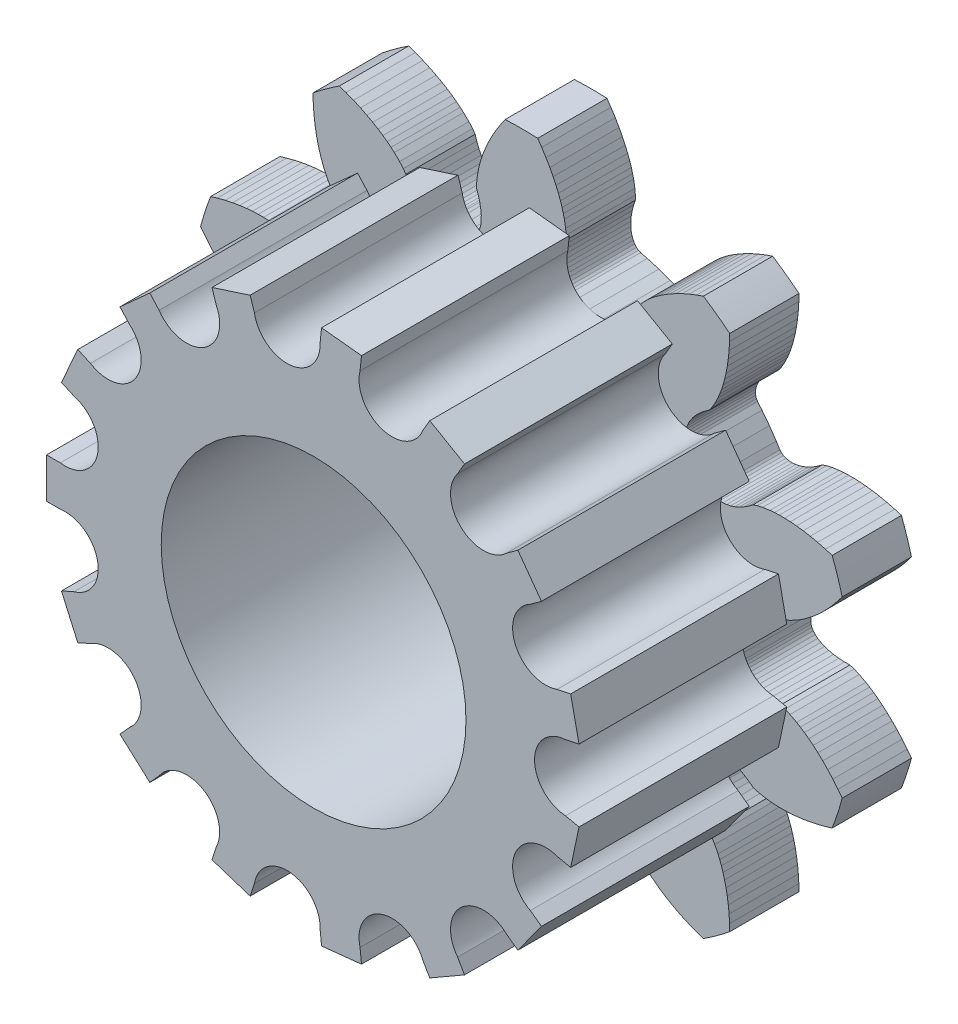
SolidWorks part; units mm, degrees
ref_plane "Front Plane" through (0, 0, 0) normal (0, 0, 1) x (1, 0, 0)
ref_plane "Top Plane" through (0, 0, 0) normal (0, 1, 0) x (1, 0, 0)
ref_plane "Right Plane" through (0, 0, 0) normal (1, 0, 0) x (0, 0, -1)
sketch "Model" plane through (0, 0, 0) normal (0, 0, 1) x (1, 0, 0)
  line L0 (44.9714, -18.1936) -> (45.0072, -17.6135)
  line L1 (45.0072, -17.6135) -> (45.064, -17.0676)
  line L2 (45.064, -17.0676) -> (45.1386, -16.5586)
  line L3 (45.1386, -16.5586) -> (45.2286, -16.0837)
  line L4 (45.2286, -16.0837) -> (45.3307, -15.6464)
  line L5 (45.3307, -15.6464) -> (45.4422, -15.245)
  line L6 (45.4422, -15.245) -> (45.5601, -14.8808)
  line L7 (45.5601, -14.8808) -> (45.6817, -14.5526)
  line L8 (45.6817, -14.5526) -> (45.8046, -14.2592)
  line L9 (45.8046, -14.2592) -> (46.0415, -13.7787)
  line L10 (46.0415, -13.7787) -> (46.2493, -13.433)
  line L11 (46.2493, -13.433) -> (46.4387, -13.1745)
  line L12 (46.4387, -13.1745) -> (46.7566, -12.9496)
  line L13 (46.7566, -12.9496) -> (47.0768, -12.6883)
  line L14 (47.0768, -12.6883) -> (47.3522, -12.4243)
  line L15 (47.3522, -12.4243) -> (47.5834, -12.1609)
  line L16 (47.5834, -12.1609) -> (47.7708, -11.9014)
  line L17 (47.7708, -11.9014) -> (47.9153, -11.6488)
  line L18 (47.9153, -11.6488) -> (48.0178, -11.4063)
  line L19 (48.0178, -11.4063) -> (48.0795, -11.177)
  line L20 (48.0795, -11.177) -> (48.1017, -10.9637)
  line L21 (48.1017, -10.9637) -> (48.086, -10.7695)
  line L22 (48.086, -10.7695) -> (48.034, -10.597)
  line L23 (48.034, -10.597) -> (47.9475, -10.4489)
  line L24 (47.9475, -10.4489) -> (47.6302, -10.0694)
  line L25 (47.6302, -10.0694) -> (47.0962, -9.3752)
  line L26 (47.0962, -9.3752) -> (46.601, -8.6528)
  line L27 (46.601, -8.6528) -> (46.3381, -8.2337)
  line L28 (46.3381, -8.2337) -> (46.224, -8.1057)
  line L29 (46.224, -8.1057) -> (46.076, -8.0029)
  line L30 (46.076, -8.0029) -> (45.8961, -7.9279)
  line L31 (45.8961, -7.9279) -> (45.6864, -7.8832)
  line L32 (45.6864, -7.8832) -> (45.4493, -7.871)
  line L33 (45.4493, -7.871) -> (45.187, -7.8936)
  line L34 (45.187, -7.8936) -> (44.9021, -7.9529)
  line L35 (44.9021, -7.9529) -> (44.5973, -8.051)
  line L36 (44.5973, -8.051) -> (44.2754, -8.1894)
  line L37 (44.2754, -8.1894) -> (43.9392, -8.3698)
  line L38 (43.9392, -8.3698) -> (43.5918, -8.5936)
  line L39 (43.5918, -8.5936) -> (43.2796, -8.8264)
  line L40 (43.2796, -8.8264) -> (42.9752, -8.9266)
  line L41 (42.9752, -8.9266) -> (42.5822, -9.0175)
  line L42 (42.5822, -9.0175) -> (42.052, -9.0943)
  line L43 (42.052, -9.0943) -> (41.735, -9.1205)
  line L44 (41.735, -9.1205) -> (41.3854, -9.1348)
  line L45 (41.3854, -9.1348) -> (41.0026, -9.1343)
  line L46 (41.0026, -9.1343) -> (40.5863, -9.1164)
  line L47 (40.5863, -9.1164) -> (40.1389, -9.0783)
  line L48 (40.1389, -9.0783) -> (39.6594, -9.0172)
  line L49 (39.6594, -9.0172) -> (39.1523, -8.9308)
  line L50 (39.1523, -8.9308) -> (38.6155, -8.8161)
  line L51 (38.6155, -8.8161) -> (38.0528, -8.671)
  line L52 (38.0528, -8.671) -> (37.565, -8.5243)
  line L53 (36.8392, -6.2906) -> (37.1476, -5.8853)
  line L54 (37.1476, -5.8853) -> (37.5176, -5.4371)
  line L55 (37.5176, -5.4371) -> (37.8845, -5.0288)
  line L56 (37.8845, -5.0288) -> (38.244, -4.6608)
  line L57 (38.244, -4.6608) -> (38.596, -4.3295)
  line L58 (38.596, -4.3295) -> (38.9355, -4.0358)
  line L59 (38.9355, -4.0358) -> (39.2618, -3.7766)
  line L60 (39.2618, -3.7766) -> (39.5712, -3.5512)
  line L61 (39.5712, -3.5512) -> (39.8624, -3.3572)
  line L62 (39.8624, -3.3572) -> (40.1343, -3.1921)
  line L63 (40.1343, -3.1921) -> (40.6084, -2.9426)
  line L64 (40.6084, -2.9426) -> (40.9797, -2.7851)
  line L65 (40.9797, -2.7851) -> (41.2849, -2.6873)
  line L66 (41.2849, -2.6873) -> (41.6743, -2.6921)
  line L67 (41.6743, -2.6921) -> (42.0869, -2.669)
  line L68 (42.0869, -2.669) -> (42.4649, -2.6173)
  line L69 (42.4649, -2.6173) -> (42.8067, -2.5401)
  line L70 (42.8067, -2.5401) -> (43.1109, -2.4403)
  line L71 (43.1109, -2.4403) -> (43.3763, -2.3209)
  line L72 (43.3763, -2.3209) -> (43.6018, -2.1849)
  line L73 (43.6018, -2.1849) -> (43.7865, -2.0357)
  line L74 (43.7865, -2.0357) -> (43.9298, -1.8762)
  line L75 (43.9298, -1.8762) -> (44.0312, -1.7098)
  line L76 (44.0312, -1.7098) -> (44.0905, -1.5397)
  line L77 (44.0905, -1.5397) -> (44.1076, -1.369)
  line L78 (44.1076, -1.369) -> (44.074, -0.8755)
  line L79 (44.074, -0.8755) -> (44.05, 0)
  line L80 (44.05, 0) -> (44.074, 0.8755)
  line L81 (44.074, 0.8755) -> (44.1076, 1.369)
  line L82 (44.1076, 1.369) -> (44.0905, 1.5397)
  line L83 (44.0905, 1.5397) -> (44.0312, 1.7098)
  line L84 (44.0312, 1.7098) -> (43.9298, 1.8762)
  line L85 (43.9298, 1.8762) -> (43.7865, 2.0357)
  line L86 (43.7865, 2.0357) -> (43.6018, 2.1849)
  line L87 (43.6018, 2.1849) -> (43.3763, 2.3209)
  line L88 (43.3763, 2.3209) -> (43.1109, 2.4403)
  line L89 (43.1109, 2.4403) -> (42.8067, 2.5401)
  line L90 (42.8067, 2.5401) -> (42.4649, 2.6173)
  line L91 (42.4649, 2.6173) -> (42.0869, 2.669)
  line L92 (42.0869, 2.669) -> (41.6743, 2.6921)
  line L93 (41.6743, 2.6921) -> (41.2849, 2.6873)
  line L94 (41.2849, 2.6873) -> (40.9797, 2.7851)
  line L95 (40.9797, 2.7851) -> (40.6084, 2.9426)
  line L96 (40.6084, 2.9426) -> (40.1343, 3.1921)
  line L97 (40.1343, 3.1921) -> (39.8624, 3.3572)
  line L98 (39.8624, 3.3572) -> (39.5712, 3.5512)
  line L99 (39.5712, 3.5512) -> (39.2618, 3.7766)
  line L100 (39.2618, 3.7766) -> (38.9355, 4.0358)
  line L101 (38.9355, 4.0358) -> (38.596, 4.3295)
  line L102 (38.596, 4.3295) -> (38.244, 4.6608)
  line L103 (38.244, 4.6608) -> (37.8845, 5.0288)
  line L104 (37.8845, 5.0288) -> (37.5176, 5.4371)
  line L105 (37.5176, 5.4371) -> (37.1476, 5.8853)
  line L106 (37.1476, 5.8853) -> (36.8392, 6.2906)
  line L107 (37.565, 8.5243) -> (38.0528, 8.671)
  line L108 (38.0528, 8.671) -> (38.6155, 8.8161)
  line L109 (38.6155, 8.8161) -> (39.1523, 8.9308)
  line L110 (39.1523, 8.9308) -> (39.6594, 9.0172)
  line L111 (39.6594, 9.0172) -> (40.1389, 9.0783)
  line L112 (40.1389, 9.0783) -> (40.5863, 9.1164)
  line L113 (40.5863, 9.1164) -> (41.0026, 9.1343)
  line L114 (41.0026, 9.1343) -> (41.3854, 9.1348)
  line L115 (41.3854, 9.1348) -> (41.735, 9.1205)
  line L116 (41.735, 9.1205) -> (42.052, 9.0943)
  line L117 (42.052, 9.0943) -> (42.5822, 9.0175)
  line L118 (42.5822, 9.0175) -> (42.9752, 8.9266)
  line L119 (42.9752, 8.9266) -> (43.2796, 8.8264)
  line L120 (43.2796, 8.8264) -> (43.5918, 8.5936)
  line L121 (43.5918, 8.5936) -> (43.9392, 8.3698)
  line L122 (43.9392, 8.3698) -> (44.2754, 8.1894)
  line L123 (44.2754, 8.1894) -> (44.5973, 8.051)
  line L124 (44.5973, 8.051) -> (44.9021, 7.9529)
  line L125 (44.9021, 7.9529) -> (45.187, 7.8936)
  line L126 (45.187, 7.8936) -> (45.4493, 7.871)
  line L127 (45.4493, 7.871) -> (45.6864, 7.8832)
  line L128 (45.6864, 7.8832) -> (45.8961, 7.9279)
  line L129 (45.8961, 7.9279) -> (46.076, 8.0029)
  line L130 (46.076, 8.0029) -> (46.224, 8.1057)
  line L131 (46.224, 8.1057) -> (46.3381, 8.2337)
  line L132 (46.3381, 8.2337) -> (46.601, 8.6528)
  line L133 (46.601, 8.6528) -> (47.0962, 9.3752)
  line L134 (47.0962, 9.3752) -> (47.6302, 10.0694)
  line L135 (47.6302, 10.0694) -> (47.9475, 10.4489)
  line L136 (47.9475, 10.4489) -> (48.034, 10.597)
  line L137 (48.034, 10.597) -> (48.086, 10.7695)
  line L138 (48.086, 10.7695) -> (48.1017, 10.9637)
  line L139 (48.1017, 10.9637) -> (48.0795, 11.177)
  line L140 (48.0795, 11.177) -> (48.0178, 11.4063)
  line L141 (48.0178, 11.4063) -> (47.9153, 11.6488)
  line L142 (47.9153, 11.6488) -> (47.7708, 11.9014)
  line L143 (47.7708, 11.9014) -> (47.5834, 12.1609)
  line L144 (47.5834, 12.1609) -> (47.3522, 12.4243)
  line L145 (47.3522, 12.4243) -> (47.0768, 12.6883)
  line L146 (47.0768, 12.6883) -> (46.7566, 12.9496)
  line L147 (46.7566, 12.9496) -> (46.4387, 13.1745)
  line L148 (46.4387, 13.1745) -> (46.2493, 13.433)
  line L149 (46.2493, 13.433) -> (46.0415, 13.7787)
  line L150 (46.0415, 13.7787) -> (45.8046, 14.2592)
  line L151 (45.8046, 14.2592) -> (45.6817, 14.5526)
  line L152 (45.6817, 14.5526) -> (45.5601, 14.8808)
  line L153 (45.5601, 14.8808) -> (45.4422, 15.245)
  line L154 (45.4422, 15.245) -> (45.3307, 15.6464)
  line L155 (45.3307, 15.6464) -> (45.2286, 16.0837)
  line L156 (45.2286, 16.0837) -> (45.1386, 16.5586)
  line L157 (45.1386, 16.5586) -> (45.064, 17.0676)
  line L158 (45.064, 17.0676) -> (45.0072, 17.6135)
  line L159 (45.0072, 17.6135) -> (44.9714, 18.1936)
  line L160 (44.9714, 18.1936) -> (44.9601, 18.7028)
  line L161 (46.8602, 20.0833) -> (47.341, 19.9152)
  line L162 (47.341, 19.9152) -> (47.8816, 19.7019)
  line L163 (47.8816, 19.7019) -> (48.3833, 19.4792)
  line L164 (48.3833, 19.4792) -> (48.8443, 19.2509)
  line L165 (48.8443, 19.2509) -> (49.2681, 19.0186)
  line L166 (49.2681, 19.0186) -> (49.6525, 18.7864)
  line L167 (49.6525, 18.7864) -> (49.9998, 18.5562)
  line L168 (49.9998, 18.5562) -> (50.3097, 18.3316)
  line L169 (50.3097, 18.3316) -> (50.5842, 18.1146)
  line L170 (50.5842, 18.1146) -> (50.8253, 17.907)
  line L171 (50.8253, 17.907) -> (51.2091, 17.5332)
  line L172 (51.2091, 17.5332) -> (51.4736, 17.2287)
  line L173 (51.4736, 17.2287) -> (51.6609, 16.9687)
  line L174 (51.6609, 16.9687) -> (51.7767, 16.5968)
  line L175 (51.7767, 16.5968) -> (51.9262, 16.2116)
  line L176 (51.9262, 16.2116) -> (52.0921, 15.8681)
  line L177 (52.0921, 15.8681) -> (52.2712, 15.5668)
  line L178 (52.2712, 15.5668) -> (52.4601, 15.3084)
  line L179 (52.4601, 15.3084) -> (52.6557, 15.0929)
  line L180 (52.6557, 15.0929) -> (52.8547, 14.9205)
  line L181 (52.8547, 14.9205) -> (53.0537, 14.7909)
  line L182 (53.0537, 14.7909) -> (53.2496, 14.7039)
  line L183 (53.2496, 14.7039) -> (53.4392, 14.6588)
  line L184 (53.4392, 14.6588) -> (53.6194, 14.655)
  line L185 (53.6194, 14.655) -> (53.7869, 14.6915)
  line L186 (53.7869, 14.6915) -> (54.2459, 14.876)
  line L187 (54.2459, 14.876) -> (55.0712, 15.1694)
  line L188 (55.0712, 15.1694) -> (55.9113, 15.4171)
  line L189 (55.9113, 15.4171) -> (56.391, 15.5376)
  line L190 (56.391, 15.5376) -> (56.548, 15.6066)
  line L191 (56.548, 15.6066) -> (56.6915, 15.7156)
  line L192 (56.6915, 15.7156) -> (56.8184, 15.8635)
  line L193 (56.8184, 15.8635) -> (56.9258, 16.049)
  line L194 (56.9258, 16.049) -> (57.0107, 16.2708)
  line L195 (57.0107, 16.2708) -> (57.0703, 16.5273)
  line L196 (57.0703, 16.5273) -> (57.1018, 16.8165)
  line L197 (57.1018, 16.8165) -> (57.1028, 17.1367)
  line L198 (57.1028, 17.1367) -> (57.0706, 17.4857)
  line L199 (57.0706, 17.4857) -> (57.0029, 17.8611)
  line L200 (57.0029, 17.8611) -> (56.8974, 18.2607)
  line L201 (56.8974, 18.2607) -> (56.7725, 18.6296)
  line L202 (56.7725, 18.6296) -> (56.7712, 18.95)
  line L203 (56.7712, 18.95) -> (56.8063, 19.3518)
  line L204 (56.8063, 19.3518) -> (56.897, 19.8798)
  line L205 (56.897, 19.8798) -> (56.97, 20.1894)
  line L206 (56.97, 20.1894) -> (57.0646, 20.5264)
  line L207 (57.0646, 20.5264) -> (57.1833, 20.8903)
  line L208 (57.1833, 20.8903) -> (57.329, 21.2806)
  line L209 (57.329, 21.2806) -> (57.5034, 21.6944)
  line L210 (57.5034, 21.6944) -> (57.7097, 22.1315)
  line L211 (57.7097, 22.1315) -> (57.9486, 22.5871)
  line L212 (57.9486, 22.5871) -> (58.2236, 23.0622)
  line L213 (58.2236, 23.0622) -> (58.5355, 23.5525)
  line L214 (58.5355, 23.5525) -> (58.8257, 23.9711)
  line L215 (61.1743, 23.9711) -> (61.4645, 23.5525)
  line L216 (61.4645, 23.5525) -> (61.7764, 23.0622)
  line L217 (61.7764, 23.0622) -> (62.0514, 22.5871)
  line L218 (62.0514, 22.5871) -> (62.2903, 22.1315)
  line L219 (62.2903, 22.1315) -> (62.4966, 21.6944)
  line L220 (62.4966, 21.6944) -> (62.671, 21.2806)
  line L221 (62.671, 21.2806) -> (62.8167, 20.8903)
  line L222 (62.8167, 20.8903) -> (62.9354, 20.5264)
  line L223 (62.9354, 20.5264) -> (63.03, 20.1894)
  line L224 (63.03, 20.1894) -> (63.103, 19.8798)
  line L225 (63.103, 19.8798) -> (63.1937, 19.3518)
  line L226 (63.1937, 19.3518) -> (63.2288, 18.95)
  line L227 (63.2288, 18.95) -> (63.2275, 18.6296)
  line L228 (63.2275, 18.6296) -> (63.1026, 18.2607)
  line L229 (63.1026, 18.2607) -> (62.9971, 17.8611)
  line L230 (62.9971, 17.8611) -> (62.9294, 17.4857)
  line L231 (62.9294, 17.4857) -> (62.8972, 17.1367)
  line L232 (62.8972, 17.1367) -> (62.8982, 16.8165)
  line L233 (62.8982, 16.8165) -> (62.9297, 16.5273)
  line L234 (62.9297, 16.5273) -> (62.9893, 16.2708)
  line L235 (62.9893, 16.2708) -> (63.0742, 16.049)
  line L236 (63.0742, 16.049) -> (63.1816, 15.8635)
  line L237 (63.1816, 15.8635) -> (63.3085, 15.7156)
  line L238 (63.3085, 15.7156) -> (63.452, 15.6066)
  line L239 (63.452, 15.6066) -> (63.609, 15.5376)
  line L240 (63.609, 15.5376) -> (64.0887, 15.4171)
  line L241 (64.0887, 15.4171) -> (64.9288, 15.1694)
  line L242 (64.9288, 15.1694) -> (65.7541, 14.876)
  line L243 (65.7541, 14.876) -> (66.2131, 14.6915)
  line L244 (66.2131, 14.6915) -> (66.3806, 14.655)
  line L245 (66.3806, 14.655) -> (66.5608, 14.6588)
  line L246 (66.5608, 14.6588) -> (66.7504, 14.7039)
  line L247 (66.7504, 14.7039) -> (66.9463, 14.7909)
  line L248 (66.9463, 14.7909) -> (67.1453, 14.9205)
  line L249 (67.1453, 14.9205) -> (67.3443, 15.0929)
  line L250 (67.3443, 15.0929) -> (67.5399, 15.3084)
  line L251 (67.5399, 15.3084) -> (67.7288, 15.5668)
  line L252 (67.7288, 15.5668) -> (67.9079, 15.8681)
  line L253 (67.9079, 15.8681) -> (68.0738, 16.2116)
  line L254 (68.0738, 16.2116) -> (68.2233, 16.5968)
  line L255 (68.2233, 16.5968) -> (68.3391, 16.9687)
  line L256 (68.3391, 16.9687) -> (68.5264, 17.2287)
  line L257 (68.5264, 17.2287) -> (68.7909, 17.5332)
  line L258 (68.7909, 17.5332) -> (69.1747, 17.907)
  line L259 (69.1747, 17.907) -> (69.4158, 18.1146)
  line L260 (69.4158, 18.1146) -> (69.6903, 18.3316)
  line L261 (69.6903, 18.3316) -> (70.0002, 18.5562)
  line L262 (70.0002, 18.5562) -> (70.3475, 18.7864)
  line L263 (70.3475, 18.7864) -> (70.7319, 19.0186)
  line L264 (70.7319, 19.0186) -> (71.1557, 19.2509)
  line L265 (71.1557, 19.2509) -> (71.6167, 19.4792)
  line L266 (71.6167, 19.4792) -> (72.1184, 19.7019)
  line L267 (72.1184, 19.7019) -> (72.659, 19.9152)
  line L268 (72.659, 19.9152) -> (73.1398, 20.0833)
  line L269 (75.0399, 18.7028) -> (75.0286, 18.1936)
  line L270 (75.0286, 18.1936) -> (74.9928, 17.6135)
  line L271 (74.9928, 17.6135) -> (74.936, 17.0676)
  line L272 (74.936, 17.0676) -> (74.8614, 16.5586)
  line L273 (74.8614, 16.5586) -> (74.7714, 16.0837)
  line L274 (74.7714, 16.0837) -> (74.6693, 15.6464)
  line L275 (74.6693, 15.6464) -> (74.5578, 15.245)
  line L276 (74.5578, 15.245) -> (74.4399, 14.8808)
  line L277 (74.4399, 14.8808) -> (74.3183, 14.5526)
  line L278 (74.3183, 14.5526) -> (74.1954, 14.2592)
  line L279 (74.1954, 14.2592) -> (73.9585, 13.7787)
  line L280 (73.9585, 13.7787) -> (73.7507, 13.433)
  line L281 (73.7507, 13.433) -> (73.5613, 13.1745)
  line L282 (73.5613, 13.1745) -> (73.2434, 12.9496)
  line L283 (73.2434, 12.9496) -> (72.9232, 12.6883)
  line L284 (72.9232, 12.6883) -> (72.6478, 12.4243)
  line L285 (72.6478, 12.4243) -> (72.4166, 12.1609)
  line L286 (72.4166, 12.1609) -> (72.2292, 11.9014)
  line L287 (72.2292, 11.9014) -> (72.0847, 11.6488)
  line L288 (72.0847, 11.6488) -> (71.9822, 11.4063)
  line L289 (71.9822, 11.4063) -> (71.9205, 11.177)
  line L290 (71.9205, 11.177) -> (71.8983, 10.9637)
  line L291 (71.8983, 10.9637) -> (71.914, 10.7695)
  line L292 (71.914, 10.7695) -> (71.966, 10.597)
  line L293 (71.966, 10.597) -> (72.0525, 10.4489)
  line L294 (72.0525, 10.4489) -> (72.3698, 10.0694)
  line L295 (72.3698, 10.0694) -> (72.9038, 9.3752)
  line L296 (72.9038, 9.3752) -> (73.399, 8.6528)
  line L297 (73.399, 8.6528) -> (73.6619, 8.2337)
  line L298 (73.6619, 8.2337) -> (73.776, 8.1057)
  line L299 (73.776, 8.1057) -> (73.924, 8.0029)
  line L300 (73.924, 8.0029) -> (74.1039, 7.9279)
  line L301 (74.1039, 7.9279) -> (74.3136, 7.8832)
  line L302 (74.3136, 7.8832) -> (74.5507, 7.871)
  line L303 (74.5507, 7.871) -> (74.813, 7.8936)
  line L304 (74.813, 7.8936) -> (75.0979, 7.9529)
  line L305 (75.0979, 7.9529) -> (75.4027, 8.051)
  line L306 (75.4027, 8.051) -> (75.7246, 8.1894)
  line L307 (75.7246, 8.1894) -> (76.0608, 8.3698)
  line L308 (76.0608, 8.3698) -> (76.4082, 8.5936)
  line L309 (76.4082, 8.5936) -> (76.7204, 8.8264)
  line L310 (76.7204, 8.8264) -> (77.0248, 8.9266)
  line L311 (77.0248, 8.9266) -> (77.4178, 9.0175)
  line L312 (77.4178, 9.0175) -> (77.948, 9.0943)
  line L313 (77.948, 9.0943) -> (78.265, 9.1205)
  line L314 (78.265, 9.1205) -> (78.6146, 9.1348)
  line L315 (78.6146, 9.1348) -> (78.9974, 9.1343)
  line L316 (78.9974, 9.1343) -> (79.4137, 9.1164)
  line L317 (79.4137, 9.1164) -> (79.8611, 9.0783)
  line L318 (79.8611, 9.0783) -> (80.3406, 9.0172)
  line L319 (80.3406, 9.0172) -> (80.8477, 8.9308)
  line L320 (80.8477, 8.9308) -> (81.3845, 8.8161)
  line L321 (81.3845, 8.8161) -> (81.9472, 8.671)
  line L322 (81.9472, 8.671) -> (82.435, 8.5243)
  line L323 (83.1608, 6.2906) -> (82.8524, 5.8853)
  line L324 (82.8524, 5.8853) -> (82.4824, 5.4371)
  line L325 (82.4824, 5.4371) -> (82.1155, 5.0288)
  line L326 (82.1155, 5.0288) -> (81.756, 4.6608)
  line L327 (81.756, 4.6608) -> (81.4041, 4.3295)
  line L328 (81.4041, 4.3295) -> (81.0645, 4.0358)
  line L329 (81.0645, 4.0358) -> (80.7382, 3.7766)
  line L330 (80.7382, 3.7766) -> (80.4288, 3.5512)
  line L331 (80.4288, 3.5512) -> (80.1376, 3.3572)
  line L332 (80.1376, 3.3572) -> (79.8657, 3.1921)
  line L333 (79.8657, 3.1921) -> (79.3916, 2.9426)
  line L334 (79.3916, 2.9426) -> (79.0203, 2.7851)
  line L335 (79.0203, 2.7851) -> (78.7151, 2.6873)
  line L336 (78.7151, 2.6873) -> (78.3257, 2.6921)
  line L337 (78.3257, 2.6921) -> (77.9131, 2.669)
  line L338 (77.9131, 2.669) -> (77.5351, 2.6173)
  line L339 (77.5351, 2.6173) -> (77.1933, 2.5401)
  line L340 (77.1933, 2.5401) -> (76.8891, 2.4403)
  line L341 (76.8891, 2.4403) -> (76.6237, 2.3209)
  line L342 (76.6237, 2.3209) -> (76.3983, 2.1849)
  line L343 (76.3983, 2.1849) -> (76.2135, 2.0357)
  line L344 (76.2135, 2.0357) -> (76.0702, 1.8762)
  line L345 (76.0702, 1.8762) -> (75.9688, 1.7098)
  line L346 (75.9688, 1.7098) -> (75.9095, 1.5397)
  line L347 (75.9095, 1.5397) -> (75.8924, 1.369)
  line L348 (75.8924, 1.369) -> (75.926, 0.8755)
  line L349 (75.926, 0.8755) -> (75.95, 0)
  line L350 (75.95, 0) -> (75.926, -0.8755)
  line L351 (75.926, -0.8755) -> (75.8924, -1.369)
  line L352 (75.8924, -1.369) -> (75.9095, -1.5397)
  line L353 (75.9095, -1.5397) -> (75.9688, -1.7098)
  line L354 (75.9688, -1.7098) -> (76.0702, -1.8762)
  line L355 (76.0702, -1.8762) -> (76.2135, -2.0357)
  line L356 (76.2135, -2.0357) -> (76.3983, -2.1849)
  line L357 (76.3983, -2.1849) -> (76.6237, -2.3209)
  line L358 (76.6237, -2.3209) -> (76.8891, -2.4403)
  line L359 (76.8891, -2.4403) -> (77.1933, -2.5401)
  line L360 (77.1933, -2.5401) -> (77.5351, -2.6173)
  line L361 (77.5351, -2.6173) -> (77.9131, -2.669)
  line L362 (77.9131, -2.669) -> (78.3257, -2.6921)
  line L363 (78.3257, -2.6921) -> (78.7151, -2.6873)
  line L364 (78.7151, -2.6873) -> (79.0203, -2.7851)
  line L365 (79.0203, -2.7851) -> (79.3916, -2.9426)
  line L366 (79.3916, -2.9426) -> (79.8657, -3.1921)
  line L367 (79.8657, -3.1921) -> (80.1376, -3.3572)
  line L368 (80.1376, -3.3572) -> (80.4288, -3.5512)
  line L369 (80.4288, -3.5512) -> (80.7382, -3.7766)
  line L370 (80.7382, -3.7766) -> (81.0645, -4.0358)
  line L371 (81.0645, -4.0358) -> (81.4041, -4.3295)
  line L372 (81.4041, -4.3295) -> (81.756, -4.6608)
  line L373 (81.756, -4.6608) -> (82.1155, -5.0288)
  line L374 (82.1155, -5.0288) -> (82.4824, -5.4371)
  line L375 (82.4824, -5.4371) -> (82.8524, -5.8853)
  line L376 (82.8524, -5.8853) -> (83.1608, -6.2906)
  line L377 (82.435, -8.5243) -> (81.9472, -8.671)
  line L378 (81.9472, -8.671) -> (81.3845, -8.8161)
  line L379 (81.3845, -8.8161) -> (80.8477, -8.9308)
  line L380 (80.8477, -8.9308) -> (80.3406, -9.0172)
  line L381 (80.3406, -9.0172) -> (79.8611, -9.0783)
  line L382 (79.8611, -9.0783) -> (79.4137, -9.1164)
  line L383 (79.4137, -9.1164) -> (78.9974, -9.1343)
  line L384 (78.9974, -9.1343) -> (78.6146, -9.1348)
  line L385 (78.6146, -9.1348) -> (78.265, -9.1205)
  line L386 (78.265, -9.1205) -> (77.948, -9.0943)
  line L387 (77.948, -9.0943) -> (77.4178, -9.0175)
  line L388 (77.4178, -9.0175) -> (77.0248, -8.9266)
  line L389 (77.0248, -8.9266) -> (76.7204, -8.8264)
  line L390 (76.7204, -8.8264) -> (76.4082, -8.5936)
  line L391 (76.4082, -8.5936) -> (76.0608, -8.3698)
  line L392 (76.0608, -8.3698) -> (75.7246, -8.1894)
  line L393 (75.7246, -8.1894) -> (75.4027, -8.051)
  line L394 (75.4027, -8.051) -> (75.0979, -7.9529)
  line L395 (75.0979, -7.9529) -> (74.813, -7.8936)
  line L396 (74.813, -7.8936) -> (74.5507, -7.871)
  line L397 (74.5507, -7.871) -> (74.3136, -7.8832)
  line L398 (74.3136, -7.8832) -> (74.1039, -7.9279)
  line L399 (74.1039, -7.9279) -> (73.924, -8.0029)
  line L400 (73.924, -8.0029) -> (73.776, -8.1057)
  line L401 (73.776, -8.1057) -> (73.6619, -8.2337)
  line L402 (73.6619, -8.2337) -> (73.399, -8.6528)
  line L403 (73.399, -8.6528) -> (72.9038, -9.3752)
  line L404 (72.9038, -9.3752) -> (72.3698, -10.0694)
  line L405 (72.3698, -10.0694) -> (72.0525, -10.4489)
  line L406 (72.0525, -10.4489) -> (71.966, -10.597)
  line L407 (71.966, -10.597) -> (71.914, -10.7695)
  line L408 (71.914, -10.7695) -> (71.8983, -10.9637)
  line L409 (71.8983, -10.9637) -> (71.9205, -11.177)
  line L410 (71.9205, -11.177) -> (71.9822, -11.4063)
  line L411 (71.9822, -11.4063) -> (72.0847, -11.6488)
  line L412 (72.0847, -11.6488) -> (72.2292, -11.9014)
  line L413 (72.2292, -11.9014) -> (72.4166, -12.1609)
  line L414 (72.4166, -12.1609) -> (72.6478, -12.4243)
  line L415 (72.6478, -12.4243) -> (72.9232, -12.6883)
  line L416 (72.9232, -12.6883) -> (73.2434, -12.9496)
  line L417 (73.2434, -12.9496) -> (73.5613, -13.1745)
  line L418 (73.5613, -13.1745) -> (73.7507, -13.433)
  line L419 (73.7507, -13.433) -> (73.9585, -13.7787)
  line L420 (73.9585, -13.7787) -> (74.1954, -14.2592)
  line L421 (74.1954, -14.2592) -> (74.3183, -14.5526)
  line L422 (74.3183, -14.5526) -> (74.4399, -14.8808)
  line L423 (74.4399, -14.8808) -> (74.5578, -15.245)
  line L424 (74.5578, -15.245) -> (74.6693, -15.6464)
  line L425 (74.6693, -15.6464) -> (74.7714, -16.0837)
  line L426 (74.7714, -16.0837) -> (74.8614, -16.5586)
  line L427 (74.8614, -16.5586) -> (74.936, -17.0676)
  line L428 (74.936, -17.0676) -> (74.9928, -17.6135)
  line L429 (74.9928, -17.6135) -> (75.0286, -18.1936)
  line L430 (75.0286, -18.1936) -> (75.0399, -18.7028)
  line L431 (73.1398, -20.0833) -> (72.659, -19.9152)
  line L432 (72.659, -19.9152) -> (72.1184, -19.7019)
  line L433 (72.1184, -19.7019) -> (71.6167, -19.4792)
  line L434 (71.6167, -19.4792) -> (71.1557, -19.2509)
  line L435 (71.1557, -19.2509) -> (70.7319, -19.0186)
  line L436 (70.7319, -19.0186) -> (70.3475, -18.7864)
  line L437 (70.3475, -18.7864) -> (70.0002, -18.5562)
  line L438 (70.0002, -18.5562) -> (69.6903, -18.3316)
  line L439 (69.6903, -18.3316) -> (69.4158, -18.1146)
  line L440 (69.4158, -18.1146) -> (69.1747, -17.907)
  line L441 (69.1747, -17.907) -> (68.7909, -17.5332)
  line L442 (68.7909, -17.5332) -> (68.5264, -17.2287)
  line L443 (68.5264, -17.2287) -> (68.3391, -16.9687)
  line L444 (68.3391, -16.9687) -> (68.2233, -16.5968)
  line L445 (68.2233, -16.5968) -> (68.0738, -16.2116)
  line L446 (68.0738, -16.2116) -> (67.9079, -15.8681)
  line L447 (67.9079, -15.8681) -> (67.7288, -15.5668)
  line L448 (67.7288, -15.5668) -> (67.5399, -15.3084)
  line L449 (67.5399, -15.3084) -> (67.3443, -15.0929)
  line L450 (67.3443, -15.0929) -> (67.1453, -14.9205)
  line L451 (67.1453, -14.9205) -> (66.9463, -14.7909)
  line L452 (66.9463, -14.7909) -> (66.7504, -14.7039)
  line L453 (66.7504, -14.7039) -> (66.5608, -14.6588)
  line L454 (66.5608, -14.6588) -> (66.3806, -14.655)
  line L455 (66.3806, -14.655) -> (66.2131, -14.6915)
  line L456 (66.2131, -14.6915) -> (65.7541, -14.876)
  line L457 (65.7541, -14.876) -> (64.9288, -15.1694)
  line L458 (64.9288, -15.1694) -> (64.0887, -15.4171)
  line L459 (64.0887, -15.4171) -> (63.609, -15.5376)
  line L460 (63.609, -15.5376) -> (63.452, -15.6066)
  line L461 (63.452, -15.6066) -> (63.3085, -15.7156)
  line L462 (63.3085, -15.7156) -> (63.1816, -15.8635)
  line L463 (63.1816, -15.8635) -> (63.0742, -16.049)
  line L464 (63.0742, -16.049) -> (62.9893, -16.2708)
  line L465 (62.9893, -16.2708) -> (62.9297, -16.5273)
  line L466 (62.9297, -16.5273) -> (62.8982, -16.8165)
  line L467 (62.8982, -16.8165) -> (62.8972, -17.1367)
  line L468 (62.8972, -17.1367) -> (62.9294, -17.4857)
  line L469 (62.9294, -17.4857) -> (62.9971, -17.8611)
  line L470 (62.9971, -17.8611) -> (63.1026, -18.2607)
  line L471 (63.1026, -18.2607) -> (63.2275, -18.6296)
  line L472 (63.2275, -18.6296) -> (63.2288, -18.95)
  line L473 (63.2288, -18.95) -> (63.1937, -19.3518)
  line L474 (63.1937, -19.3518) -> (63.103, -19.8798)
  line L475 (63.103, -19.8798) -> (63.03, -20.1894)
  line L476 (63.03, -20.1894) -> (62.9354, -20.5264)
  line L477 (62.9354, -20.5264) -> (62.8167, -20.8903)
  line L478 (62.8167, -20.8903) -> (62.671, -21.2806)
  line L479 (62.671, -21.2806) -> (62.4966, -21.6944)
  line L480 (62.4966, -21.6944) -> (62.2903, -22.1315)
  line L481 (62.2903, -22.1315) -> (62.0514, -22.5871)
  line L482 (62.0514, -22.5871) -> (61.7764, -23.0622)
  line L483 (61.7764, -23.0622) -> (61.4645, -23.5525)
  line L484 (61.4645, -23.5525) -> (61.1743, -23.9711)
  line L485 (58.8257, -23.9711) -> (58.5355, -23.5525)
  line L486 (58.5355, -23.5525) -> (58.2236, -23.0622)
  line L487 (58.2236, -23.0622) -> (57.9486, -22.5871)
  line L488 (57.9486, -22.5871) -> (57.7097, -22.1315)
  line L489 (57.7097, -22.1315) -> (57.5034, -21.6944)
  line L490 (57.5034, -21.6944) -> (57.329, -21.2806)
  line L491 (57.329, -21.2806) -> (57.1833, -20.8903)
  line L492 (57.1833, -20.8903) -> (57.0646, -20.5264)
  line L493 (57.0646, -20.5264) -> (56.97, -20.1894)
  line L494 (56.97, -20.1894) -> (56.897, -19.8798)
  line L495 (56.897, -19.8798) -> (56.8063, -19.3518)
  line L496 (56.8063, -19.3518) -> (56.7712, -18.95)
  line L497 (56.7712, -18.95) -> (56.7725, -18.6296)
  line L498 (56.7725, -18.6296) -> (56.8974, -18.2607)
  line L499 (56.8974, -18.2607) -> (57.0029, -17.8611)
  line L500 (57.0029, -17.8611) -> (57.0706, -17.4857)
  line L501 (57.0706, -17.4857) -> (57.1028, -17.1367)
  line L502 (57.1028, -17.1367) -> (57.1018, -16.8165)
  line L503 (57.1018, -16.8165) -> (57.0703, -16.5273)
  line L504 (57.0703, -16.5273) -> (57.0107, -16.2708)
  line L505 (57.0107, -16.2708) -> (56.9258, -16.049)
  line L506 (56.9258, -16.049) -> (56.8184, -15.8635)
  line L507 (56.8184, -15.8635) -> (56.6915, -15.7156)
  line L508 (56.6915, -15.7156) -> (56.548, -15.6066)
  line L509 (56.548, -15.6066) -> (56.391, -15.5376)
  line L510 (56.391, -15.5376) -> (55.9113, -15.4171)
  line L511 (55.9113, -15.4171) -> (55.0712, -15.1694)
  line L512 (55.0712, -15.1694) -> (54.2459, -14.876)
  line L513 (54.2459, -14.876) -> (53.7869, -14.6915)
  line L514 (53.7869, -14.6915) -> (53.6194, -14.655)
  line L515 (53.6194, -14.655) -> (53.4392, -14.6588)
  line L516 (53.4392, -14.6588) -> (53.2496, -14.7039)
  line L517 (53.2496, -14.7039) -> (53.0537, -14.7909)
  line L518 (53.0537, -14.7909) -> (52.8547, -14.9205)
  line L519 (52.8547, -14.9205) -> (52.6557, -15.0929)
  line L520 (52.6557, -15.0929) -> (52.4601, -15.3084)
  line L521 (52.4601, -15.3084) -> (52.2712, -15.5668)
  line L522 (52.2712, -15.5668) -> (52.0921, -15.8681)
  line L523 (52.0921, -15.8681) -> (51.9262, -16.2116)
  line L524 (51.9262, -16.2116) -> (51.7767, -16.5968)
  line L525 (51.7767, -16.5968) -> (51.6609, -16.9687)
  line L526 (51.6609, -16.9687) -> (51.4736, -17.2287)
  line L527 (51.4736, -17.2287) -> (51.2091, -17.5332)
  line L528 (51.2091, -17.5332) -> (50.8253, -17.907)
  line L529 (50.8253, -17.907) -> (50.5842, -18.1146)
  line L530 (50.5842, -18.1146) -> (50.3097, -18.3316)
  line L531 (50.3097, -18.3316) -> (49.9998, -18.5562)
  line L532 (49.9998, -18.5562) -> (49.6525, -18.7864)
  line L533 (49.6525, -18.7864) -> (49.2681, -19.0186)
  line L534 (49.2681, -19.0186) -> (48.8443, -19.2509)
  line L535 (48.8443, -19.2509) -> (48.3833, -19.4792)
  line L536 (48.3833, -19.4792) -> (47.8816, -19.7019)
  line L537 (47.8816, -19.7019) -> (47.341, -19.9152)
  line L538 (47.341, -19.9152) -> (46.8602, -20.0833)
  line L539 (44.9601, -18.7028) -> (44.9714, -18.1936)
  line L540 (44.9714, -18.1936) -> (45.0072, -17.6135)
  line L541 (45.0072, -17.6135) -> (45.064, -17.0676)
  line L542 (45.064, -17.0676) -> (45.1386, -16.5586)
  line L543 (45.1386, -16.5586) -> (45.2286, -16.0837)
  line L544 (45.2286, -16.0837) -> (45.3307, -15.6464)
  line L545 (45.3307, -15.6464) -> (45.4422, -15.245)
  line L546 (45.4422, -15.245) -> (45.5601, -14.8808)
  line L547 (45.5601, -14.8808) -> (45.6817, -14.5526)
  line L548 (45.6817, -14.5526) -> (45.8046, -14.2592)
  line L549 (45.8046, -14.2592) -> (46.0415, -13.7787)
  line L550 (46.0415, -13.7787) -> (46.2493, -13.433)
  line L551 (46.2493, -13.433) -> (46.4387, -13.1745)
  line L552 (46.4387, -13.1745) -> (46.7566, -12.9496)
  line L553 (46.7566, -12.9496) -> (47.0768, -12.6883)
  line L554 (47.0768, -12.6883) -> (47.3522, -12.4243)
  line L555 (47.3522, -12.4243) -> (47.5834, -12.1609)
  line L556 (47.5834, -12.1609) -> (47.7708, -11.9014)
  line L557 (47.7708, -11.9014) -> (47.9153, -11.6488)
  line L558 (47.9153, -11.6488) -> (48.0178, -11.4063)
  line L559 (48.0178, -11.4063) -> (48.0795, -11.177)
  line L560 (48.0795, -11.177) -> (48.1017, -10.9637)
  line L561 (48.1017, -10.9637) -> (48.086, -10.7695)
  line L562 (48.086, -10.7695) -> (48.034, -10.597)
  line L563 (48.034, -10.597) -> (47.9475, -10.4489)
  line L564 (47.9475, -10.4489) -> (47.6302, -10.0694)
  line L565 (47.6302, -10.0694) -> (47.0962, -9.3752)
  line L566 (47.0962, -9.3752) -> (46.601, -8.6528)
  line L567 (46.601, -8.6528) -> (46.3381, -8.2337)
  line L568 (46.3381, -8.2337) -> (46.224, -8.1057)
  line L569 (46.224, -8.1057) -> (46.076, -8.0029)
  line L570 (46.076, -8.0029) -> (45.8961, -7.9279)
  line L571 (45.8961, -7.9279) -> (45.6864, -7.8832)
  line L572 (45.6864, -7.8832) -> (45.4493, -7.871)
  line L573 (45.4493, -7.871) -> (45.187, -7.8936)
  line L574 (45.187, -7.8936) -> (44.9021, -7.9529)
  line L575 (44.9021, -7.9529) -> (44.5973, -8.051)
  line L576 (44.5973, -8.051) -> (44.2754, -8.1894)
  line L577 (44.2754, -8.1894) -> (43.9392, -8.3698)
  line L578 (43.9392, -8.3698) -> (43.5918, -8.5936)
  line L579 (43.5918, -8.5936) -> (43.2796, -8.8264)
  line L580 (43.2796, -8.8264) -> (42.9752, -8.9266)
  line L581 (42.9752, -8.9266) -> (42.5822, -9.0175)
  line L582 (42.5822, -9.0175) -> (42.052, -9.0943)
  line L583 (42.052, -9.0943) -> (41.735, -9.1205)
  line L584 (41.735, -9.1205) -> (41.3854, -9.1348)
  line L585 (41.3854, -9.1348) -> (41.0026, -9.1343)
  line L586 (41.0026, -9.1343) -> (40.5863, -9.1164)
  line L587 (40.5863, -9.1164) -> (40.1389, -9.0783)
  line L588 (40.1389, -9.0783) -> (39.6594, -9.0172)
  line L589 (39.6594, -9.0172) -> (39.1523, -8.9308)
  line L590 (39.1523, -8.9308) -> (38.6155, -8.8161)
  line L591 (38.6155, -8.8161) -> (38.0528, -8.671)
  line L592 (38.0528, -8.671) -> (37.565, -8.5243)
  line L593 (36.8392, -6.2906) -> (37.1476, -5.8853)
  line L594 (37.1476, -5.8853) -> (37.5176, -5.4371)
  line L595 (37.5176, -5.4371) -> (37.8845, -5.0288)
  line L596 (37.8845, -5.0288) -> (38.244, -4.6608)
  line L597 (38.244, -4.6608) -> (38.596, -4.3295)
  line L598 (38.596, -4.3295) -> (38.9355, -4.0358)
  line L599 (38.9355, -4.0358) -> (39.2618, -3.7766)
  line L600 (39.2618, -3.7766) -> (39.5712, -3.5512)
  line L601 (39.5712, -3.5512) -> (39.8624, -3.3572)
  line L602 (39.8624, -3.3572) -> (40.1343, -3.1921)
  line L603 (40.1343, -3.1921) -> (40.6084, -2.9426)
  line L604 (40.6084, -2.9426) -> (40.9797, -2.7851)
  line L605 (40.9797, -2.7851) -> (41.2849, -2.6873)
  line L606 (41.2849, -2.6873) -> (41.6743, -2.6921)
  line L607 (41.6743, -2.6921) -> (42.0869, -2.669)
  line L608 (42.0869, -2.669) -> (42.4649, -2.6173)
  line L609 (42.4649, -2.6173) -> (42.8067, -2.5401)
  line L610 (42.8067, -2.5401) -> (43.1109, -2.4403)
  line L611 (43.1109, -2.4403) -> (43.3763, -2.3209)
  line L612 (43.3763, -2.3209) -> (43.6018, -2.1849)
  line L613 (43.6018, -2.1849) -> (43.7865, -2.0357)
  line L614 (43.7865, -2.0357) -> (43.9298, -1.8762)
  line L615 (43.9298, -1.8762) -> (44.0312, -1.7098)
  line L616 (44.0312, -1.7098) -> (44.0905, -1.5397)
  line L617 (44.0905, -1.5397) -> (44.1076, -1.369)
  line L618 (44.1076, -1.369) -> (44.074, -0.8755)
  line L619 (44.074, -0.8755) -> (44.05, 0)
  line L620 (44.05, 0) -> (44.074, 0.8755)
  line L621 (44.074, 0.8755) -> (44.1076, 1.369)
  line L622 (44.1076, 1.369) -> (44.0905, 1.5397)
  line L623 (44.0905, 1.5397) -> (44.0312, 1.7098)
  line L624 (44.0312, 1.7098) -> (43.9298, 1.8762)
  line L625 (43.9298, 1.8762) -> (43.7865, 2.0357)
  line L626 (43.7865, 2.0357) -> (43.6018, 2.1849)
  line L627 (43.6018, 2.1849) -> (43.3763, 2.3209)
  line L628 (43.3763, 2.3209) -> (43.1109, 2.4403)
  line L629 (43.1109, 2.4403) -> (42.8067, 2.5401)
  line L630 (42.8067, 2.5401) -> (42.4649, 2.6173)
  line L631 (42.4649, 2.6173) -> (42.0869, 2.669)
  line L632 (42.0869, 2.669) -> (41.6743, 2.6921)
  line L633 (41.6743, 2.6921) -> (41.2849, 2.6873)
  line L634 (41.2849, 2.6873) -> (40.9797, 2.7851)
  line L635 (40.9797, 2.7851) -> (40.6084, 2.9426)
  line L636 (40.6084, 2.9426) -> (40.1343, 3.1921)
  line L637 (40.1343, 3.1921) -> (39.8624, 3.3572)
  line L638 (39.8624, 3.3572) -> (39.5712, 3.5512)
  line L639 (39.5712, 3.5512) -> (39.2618, 3.7766)
  line L640 (39.2618, 3.7766) -> (38.9355, 4.0358)
  line L641 (38.9355, 4.0358) -> (38.596, 4.3295)
  line L642 (38.596, 4.3295) -> (38.244, 4.6608)
  line L643 (38.244, 4.6608) -> (37.8845, 5.0288)
  line L644 (37.8845, 5.0288) -> (37.5176, 5.4371)
  line L645 (37.5176, 5.4371) -> (37.1476, 5.8853)
  line L646 (37.1476, 5.8853) -> (36.8392, 6.2906)
  line L647 (37.565, 8.5243) -> (38.0528, 8.671)
  line L648 (38.0528, 8.671) -> (38.6155, 8.8161)
  line L649 (38.6155, 8.8161) -> (39.1523, 8.9308)
  line L650 (39.1523, 8.9308) -> (39.6594, 9.0172)
  line L651 (39.6594, 9.0172) -> (40.1389, 9.0783)
  line L652 (40.1389, 9.0783) -> (40.5863, 9.1164)
  line L653 (40.5863, 9.1164) -> (41.0026, 9.1343)
  line L654 (41.0026, 9.1343) -> (41.3854, 9.1348)
  line L655 (41.3854, 9.1348) -> (41.735, 9.1205)
  line L656 (41.735, 9.1205) -> (42.052, 9.0943)
  line L657 (42.052, 9.0943) -> (42.5822, 9.0175)
  line L658 (42.5822, 9.0175) -> (42.9752, 8.9266)
  line L659 (42.9752, 8.9266) -> (43.2796, 8.8264)
  line L660 (43.2796, 8.8264) -> (43.5918, 8.5936)
  line L661 (43.5918, 8.5936) -> (43.9392, 8.3698)
  line L662 (43.9392, 8.3698) -> (44.2754, 8.1894)
  line L663 (44.2754, 8.1894) -> (44.5973, 8.051)
  line L664 (44.5973, 8.051) -> (44.9021, 7.9529)
  line L665 (44.9021, 7.9529) -> (45.187, 7.8936)
  line L666 (45.187, 7.8936) -> (45.4493, 7.871)
  line L667 (45.4493, 7.871) -> (45.6864, 7.8832)
  line L668 (45.6864, 7.8832) -> (45.8961, 7.9279)
  line L669 (45.8961, 7.9279) -> (46.076, 8.0029)
  line L670 (46.076, 8.0029) -> (46.224, 8.1057)
  line L671 (46.224, 8.1057) -> (46.3381, 8.2337)
  line L672 (46.3381, 8.2337) -> (46.601, 8.6528)
  line L673 (46.601, 8.6528) -> (47.0962, 9.3752)
  line L674 (47.0962, 9.3752) -> (47.6302, 10.0694)
  line L675 (47.6302, 10.0694) -> (47.9475, 10.4489)
  line L676 (47.9475, 10.4489) -> (48.034, 10.597)
  line L677 (48.034, 10.597) -> (48.086, 10.7695)
  line L678 (48.086, 10.7695) -> (48.1017, 10.9637)
  line L679 (48.1017, 10.9637) -> (48.0795, 11.177)
  line L680 (48.0795, 11.177) -> (48.0178, 11.4063)
  line L681 (48.0178, 11.4063) -> (47.9153, 11.6488)
  line L682 (47.9153, 11.6488) -> (47.7708, 11.9014)
  line L683 (47.7708, 11.9014) -> (47.5834, 12.1609)
  line L684 (47.5834, 12.1609) -> (47.3522, 12.4243)
  line L685 (47.3522, 12.4243) -> (47.0768, 12.6883)
  line L686 (47.0768, 12.6883) -> (46.7566, 12.9496)
  line L687 (46.7566, 12.9496) -> (46.4387, 13.1745)
  line L688 (46.4387, 13.1745) -> (46.2493, 13.433)
  line L689 (46.2493, 13.433) -> (46.0415, 13.7787)
  line L690 (46.0415, 13.7787) -> (45.8046, 14.2592)
  line L691 (45.8046, 14.2592) -> (45.6817, 14.5526)
  line L692 (45.6817, 14.5526) -> (45.5601, 14.8808)
  line L693 (45.5601, 14.8808) -> (45.4422, 15.245)
  line L694 (45.4422, 15.245) -> (45.3307, 15.6464)
  line L695 (45.3307, 15.6464) -> (45.2286, 16.0837)
  line L696 (45.2286, 16.0837) -> (45.1386, 16.5586)
  line L697 (45.1386, 16.5586) -> (45.064, 17.0676)
  line L698 (45.064, 17.0676) -> (45.0072, 17.6135)
  line L699 (45.0072, 17.6135) -> (44.9714, 18.1936)
  line L700 (44.9714, 18.1936) -> (44.9601, 18.7028)
  line L701 (46.8602, 20.0833) -> (47.341, 19.9152)
  line L702 (47.341, 19.9152) -> (47.8816, 19.7019)
  line L703 (47.8816, 19.7019) -> (48.3833, 19.4792)
  line L704 (48.3833, 19.4792) -> (48.8443, 19.2509)
  line L705 (48.8443, 19.2509) -> (49.2681, 19.0186)
  line L706 (49.2681, 19.0186) -> (49.6525, 18.7864)
  line L707 (49.6525, 18.7864) -> (49.9998, 18.5562)
  line L708 (49.9998, 18.5562) -> (50.3097, 18.3316)
  line L709 (50.3097, 18.3316) -> (50.5842, 18.1146)
  line L710 (50.5842, 18.1146) -> (50.8253, 17.907)
  line L711 (50.8253, 17.907) -> (51.2091, 17.5332)
  line L712 (51.2091, 17.5332) -> (51.4736, 17.2287)
  line L713 (51.4736, 17.2287) -> (51.6609, 16.9687)
  line L714 (51.6609, 16.9687) -> (51.7767, 16.5968)
  line L715 (51.7767, 16.5968) -> (51.9262, 16.2116)
  line L716 (51.9262, 16.2116) -> (52.0921, 15.8681)
  line L717 (52.0921, 15.8681) -> (52.2712, 15.5668)
  line L718 (52.2712, 15.5668) -> (52.4601, 15.3084)
  line L719 (52.4601, 15.3084) -> (52.6557, 15.0929)
  line L720 (52.6557, 15.0929) -> (52.8547, 14.9205)
  line L721 (52.8547, 14.9205) -> (53.0537, 14.7909)
  line L722 (53.0537, 14.7909) -> (53.2496, 14.7039)
  line L723 (53.2496, 14.7039) -> (53.4392, 14.6588)
  line L724 (53.4392, 14.6588) -> (53.6194, 14.655)
  line L725 (53.6194, 14.655) -> (53.7869, 14.6915)
  line L726 (53.7869, 14.6915) -> (54.2459, 14.876)
  line L727 (54.2459, 14.876) -> (55.0712, 15.1694)
  line L728 (55.0712, 15.1694) -> (55.9113, 15.4171)
  line L729 (55.9113, 15.4171) -> (56.391, 15.5376)
  line L730 (56.391, 15.5376) -> (56.548, 15.6066)
  line L731 (56.548, 15.6066) -> (56.6915, 15.7156)
  line L732 (56.6915, 15.7156) -> (56.8184, 15.8635)
  line L733 (56.8184, 15.8635) -> (56.9258, 16.049)
  line L734 (56.9258, 16.049) -> (57.0107, 16.2708)
  line L735 (57.0107, 16.2708) -> (57.0703, 16.5273)
  line L736 (57.0703, 16.5273) -> (57.1018, 16.8165)
  line L737 (57.1018, 16.8165) -> (57.1028, 17.1367)
  line L738 (57.1028, 17.1367) -> (57.0706, 17.4857)
  line L739 (57.0706, 17.4857) -> (57.0029, 17.8611)
  line L740 (57.0029, 17.8611) -> (56.8974, 18.2607)
  line L741 (56.8974, 18.2607) -> (56.7725, 18.6296)
  line L742 (56.7725, 18.6296) -> (56.7712, 18.95)
  line L743 (56.7712, 18.95) -> (56.8063, 19.3518)
  line L744 (56.8063, 19.3518) -> (56.897, 19.8798)
  line L745 (56.897, 19.8798) -> (56.97, 20.1894)
  line L746 (56.97, 20.1894) -> (57.0646, 20.5264)
  line L747 (57.0646, 20.5264) -> (57.1833, 20.8903)
  line L748 (57.1833, 20.8903) -> (57.329, 21.2806)
  line L749 (57.329, 21.2806) -> (57.5034, 21.6944)
  line L750 (57.5034, 21.6944) -> (57.7097, 22.1315)
  line L751 (57.7097, 22.1315) -> (57.9486, 22.5871)
  line L752 (57.9486, 22.5871) -> (58.2236, 23.0622)
  line L753 (58.2236, 23.0622) -> (58.5355, 23.5525)
  line L754 (58.5355, 23.5525) -> (58.8257, 23.9711)
  line L755 (61.1743, 23.9711) -> (61.4645, 23.5525)
  line L756 (61.4645, 23.5525) -> (61.7764, 23.0622)
  line L757 (61.7764, 23.0622) -> (62.0514, 22.5871)
  line L758 (62.0514, 22.5871) -> (62.2903, 22.1315)
  line L759 (62.2903, 22.1315) -> (62.4966, 21.6944)
  line L760 (62.4966, 21.6944) -> (62.671, 21.2806)
  line L761 (62.671, 21.2806) -> (62.8167, 20.8903)
  line L762 (62.8167, 20.8903) -> (62.9354, 20.5264)
  line L763 (62.9354, 20.5264) -> (63.03, 20.1894)
  line L764 (63.03, 20.1894) -> (63.103, 19.8798)
  line L765 (63.103, 19.8798) -> (63.1937, 19.3518)
  line L766 (63.1937, 19.3518) -> (63.2288, 18.95)
  line L767 (63.2288, 18.95) -> (63.2275, 18.6296)
  line L768 (63.2275, 18.6296) -> (63.1026, 18.2607)
  line L769 (63.1026, 18.2607) -> (62.9971, 17.8611)
  line L770 (62.9971, 17.8611) -> (62.9294, 17.4857)
  line L771 (62.9294, 17.4857) -> (62.8972, 17.1367)
  line L772 (62.8972, 17.1367) -> (62.8982, 16.8165)
  line L773 (62.8982, 16.8165) -> (62.9297, 16.5273)
  line L774 (62.9297, 16.5273) -> (62.9893, 16.2708)
  line L775 (62.9893, 16.2708) -> (63.0742, 16.049)
  line L776 (63.0742, 16.049) -> (63.1816, 15.8635)
  line L777 (63.1816, 15.8635) -> (63.3085, 15.7156)
  line L778 (63.3085, 15.7156) -> (63.452, 15.6066)
  line L779 (63.452, 15.6066) -> (63.609, 15.5376)
  line L780 (63.609, 15.5376) -> (64.0887, 15.4171)
  line L781 (64.0887, 15.4171) -> (64.9288, 15.1694)
  line L782 (64.9288, 15.1694) -> (65.7541, 14.876)
  line L783 (65.7541, 14.876) -> (66.2131, 14.6915)
  line L784 (66.2131, 14.6915) -> (66.3806, 14.655)
  line L785 (66.3806, 14.655) -> (66.5608, 14.6588)
  line L786 (66.5608, 14.6588) -> (66.7504, 14.7039)
  line L787 (66.7504, 14.7039) -> (66.9463, 14.7909)
  line L788 (66.9463, 14.7909) -> (67.1453, 14.9205)
  line L789 (67.1453, 14.9205) -> (67.3443, 15.0929)
  line L790 (67.3443, 15.0929) -> (67.5399, 15.3084)
  line L791 (67.5399, 15.3084) -> (67.7288, 15.5668)
  line L792 (67.7288, 15.5668) -> (67.9079, 15.8681)
  line L793 (67.9079, 15.8681) -> (68.0738, 16.2116)
  line L794 (68.0738, 16.2116) -> (68.2233, 16.5968)
  line L795 (68.2233, 16.5968) -> (68.3391, 16.9687)
  line L796 (68.3391, 16.9687) -> (68.5264, 17.2287)
  line L797 (68.5264, 17.2287) -> (68.7909, 17.5332)
  line L798 (68.7909, 17.5332) -> (69.1747, 17.907)
  line L799 (69.1747, 17.907) -> (69.4158, 18.1146)
  line L800 (69.4158, 18.1146) -> (69.6903, 18.3316)
  line L801 (69.6903, 18.3316) -> (70.0002, 18.5562)
  line L802 (70.0002, 18.5562) -> (70.3475, 18.7864)
  line L803 (70.3475, 18.7864) -> (70.7319, 19.0186)
  line L804 (70.7319, 19.0186) -> (71.1557, 19.2509)
  line L805 (71.1557, 19.2509) -> (71.6167, 19.4792)
  line L806 (71.6167, 19.4792) -> (72.1184, 19.7019)
  line L807 (72.1184, 19.7019) -> (72.659, 19.9152)
  line L808 (72.659, 19.9152) -> (73.1398, 20.0833)
  line L809 (75.0399, 18.7028) -> (75.0286, 18.1936)
  line L810 (75.0286, 18.1936) -> (74.9928, 17.6135)
  line L811 (74.9928, 17.6135) -> (74.936, 17.0676)
  line L812 (74.936, 17.0676) -> (74.8614, 16.5586)
  line L813 (74.8614, 16.5586) -> (74.7714, 16.0837)
  line L814 (74.7714, 16.0837) -> (74.6693, 15.6464)
  line L815 (74.6693, 15.6464) -> (74.5578, 15.245)
  line L816 (74.5578, 15.245) -> (74.4399, 14.8808)
  line L817 (74.4399, 14.8808) -> (74.3183, 14.5526)
  line L818 (74.3183, 14.5526) -> (74.1954, 14.2592)
  line L819 (74.1954, 14.2592) -> (73.9585, 13.7787)
  line L820 (73.9585, 13.7787) -> (73.7507, 13.433)
  line L821 (73.7507, 13.433) -> (73.5613, 13.1745)
  line L822 (73.5613, 13.1745) -> (73.2434, 12.9496)
  line L823 (73.2434, 12.9496) -> (72.9232, 12.6883)
  line L824 (72.9232, 12.6883) -> (72.6478, 12.4243)
  line L825 (72.6478, 12.4243) -> (72.4166, 12.1609)
  line L826 (72.4166, 12.1609) -> (72.2292, 11.9014)
  line L827 (72.2292, 11.9014) -> (72.0847, 11.6488)
  line L828 (72.0847, 11.6488) -> (71.9822, 11.4063)
  line L829 (71.9822, 11.4063) -> (71.9205, 11.177)
  line L830 (71.9205, 11.177) -> (71.8983, 10.9637)
  line L831 (71.8983, 10.9637) -> (71.914, 10.7695)
  line L832 (71.914, 10.7695) -> (71.966, 10.597)
  line L833 (71.966, 10.597) -> (72.0525, 10.4489)
  line L834 (72.0525, 10.4489) -> (72.3698, 10.0694)
  line L835 (72.3698, 10.0694) -> (72.9038, 9.3752)
  line L836 (72.9038, 9.3752) -> (73.399, 8.6528)
  line L837 (73.399, 8.6528) -> (73.6619, 8.2337)
  line L838 (73.6619, 8.2337) -> (73.776, 8.1057)
  line L839 (73.776, 8.1057) -> (73.924, 8.0029)
  line L840 (73.924, 8.0029) -> (74.1039, 7.9279)
  line L841 (74.1039, 7.9279) -> (74.3136, 7.8832)
  line L842 (74.3136, 7.8832) -> (74.5507, 7.871)
  line L843 (74.5507, 7.871) -> (74.813, 7.8936)
  line L844 (74.813, 7.8936) -> (75.0979, 7.9529)
  line L845 (75.0979, 7.9529) -> (75.4027, 8.051)
  line L846 (75.4027, 8.051) -> (75.7246, 8.1894)
  line L847 (75.7246, 8.1894) -> (76.0608, 8.3698)
  line L848 (76.0608, 8.3698) -> (76.4082, 8.5936)
  line L849 (76.4082, 8.5936) -> (76.7204, 8.8264)
  line L850 (76.7204, 8.8264) -> (77.0248, 8.9266)
  line L851 (77.0248, 8.9266) -> (77.4178, 9.0175)
  line L852 (77.4178, 9.0175) -> (77.948, 9.0943)
  line L853 (77.948, 9.0943) -> (78.265, 9.1205)
  line L854 (78.265, 9.1205) -> (78.6146, 9.1348)
  line L855 (78.6146, 9.1348) -> (78.9974, 9.1343)
  line L856 (78.9974, 9.1343) -> (79.4137, 9.1164)
  line L857 (79.4137, 9.1164) -> (79.8611, 9.0783)
  line L858 (79.8611, 9.0783) -> (80.3406, 9.0172)
  line L859 (80.3406, 9.0172) -> (80.8477, 8.9308)
  line L860 (80.8477, 8.9308) -> (81.3845, 8.8161)
  line L861 (81.3845, 8.8161) -> (81.9472, 8.671)
  line L862 (81.9472, 8.671) -> (82.435, 8.5243)
  line L863 (83.1608, 6.2906) -> (82.8524, 5.8853)
  line L864 (82.8524, 5.8853) -> (82.4824, 5.4371)
  line L865 (82.4824, 5.4371) -> (82.1155, 5.0288)
  line L866 (82.1155, 5.0288) -> (81.756, 4.6608)
  line L867 (81.756, 4.6608) -> (81.4041, 4.3295)
  line L868 (81.4041, 4.3295) -> (81.0645, 4.0358)
  line L869 (81.0645, 4.0358) -> (80.7382, 3.7766)
  line L870 (80.7382, 3.7766) -> (80.4288, 3.5512)
  line L871 (80.4288, 3.5512) -> (80.1376, 3.3572)
  line L872 (80.1376, 3.3572) -> (79.8657, 3.1921)
  line L873 (79.8657, 3.1921) -> (79.3916, 2.9426)
  line L874 (79.3916, 2.9426) -> (79.0203, 2.7851)
  line L875 (79.0203, 2.7851) -> (78.7151, 2.6873)
  line L876 (78.7151, 2.6873) -> (78.3257, 2.6921)
  line L877 (78.3257, 2.6921) -> (77.9131, 2.669)
  line L878 (77.9131, 2.669) -> (77.5351, 2.6173)
  line L879 (77.5351, 2.6173) -> (77.1933, 2.5401)
  line L880 (77.1933, 2.5401) -> (76.8891, 2.4403)
  line L881 (76.8891, 2.4403) -> (76.6237, 2.3209)
  line L882 (76.6237, 2.3209) -> (76.3983, 2.1849)
  line L883 (76.3983, 2.1849) -> (76.2135, 2.0357)
  line L884 (76.2135, 2.0357) -> (76.0702, 1.8762)
  line L885 (76.0702, 1.8762) -> (75.9688, 1.7098)
  line L886 (75.9688, 1.7098) -> (75.9095, 1.5397)
  line L887 (75.9095, 1.5397) -> (75.8924, 1.369)
  line L888 (75.8924, 1.369) -> (75.926, 0.8755)
  line L889 (75.926, 0.8755) -> (75.95, 0)
  line L890 (75.95, 0) -> (75.926, -0.8755)
  line L891 (75.926, -0.8755) -> (75.8924, -1.369)
  line L892 (75.8924, -1.369) -> (75.9095, -1.5397)
  line L893 (75.9095, -1.5397) -> (75.9688, -1.7098)
  line L894 (75.9688, -1.7098) -> (76.0702, -1.8762)
  line L895 (76.0702, -1.8762) -> (76.2135, -2.0357)
  line L896 (76.2135, -2.0357) -> (76.3983, -2.1849)
  line L897 (76.3983, -2.1849) -> (76.6237, -2.3209)
  line L898 (76.6237, -2.3209) -> (76.8891, -2.4403)
  line L899 (76.8891, -2.4403) -> (77.1933, -2.5401)
  line L900 (77.1933, -2.5401) -> (77.5351, -2.6173)
  line L901 (77.5351, -2.6173) -> (77.9131, -2.669)
  line L902 (77.9131, -2.669) -> (78.3257, -2.6921)
  line L903 (78.3257, -2.6921) -> (78.7151, -2.6873)
  line L904 (78.7151, -2.6873) -> (79.0203, -2.7851)
  line L905 (79.0203, -2.7851) -> (79.3916, -2.9426)
  line L906 (79.3916, -2.9426) -> (79.8657, -3.1921)
  line L907 (79.8657, -3.1921) -> (80.1376, -3.3572)
  line L908 (80.1376, -3.3572) -> (80.4288, -3.5512)
  line L909 (80.4288, -3.5512) -> (80.7382, -3.7766)
  line L910 (80.7382, -3.7766) -> (81.0645, -4.0358)
  line L911 (81.0645, -4.0358) -> (81.4041, -4.3295)
  line L912 (81.4041, -4.3295) -> (81.756, -4.6608)
  line L913 (81.756, -4.6608) -> (82.1155, -5.0288)
  line L914 (82.1155, -5.0288) -> (82.4824, -5.4371)
  line L915 (82.4824, -5.4371) -> (82.8524, -5.8853)
  line L916 (82.8524, -5.8853) -> (83.1608, -6.2906)
  line L917 (82.435, -8.5243) -> (81.9472, -8.671)
  line L918 (81.9472, -8.671) -> (81.3845, -8.8161)
  line L919 (81.3845, -8.8161) -> (80.8477, -8.9308)
  line L920 (80.8477, -8.9308) -> (80.3406, -9.0172)
  line L921 (80.3406, -9.0172) -> (79.8611, -9.0783)
  line L922 (79.8611, -9.0783) -> (79.4137, -9.1164)
  line L923 (79.4137, -9.1164) -> (78.9974, -9.1343)
  line L924 (78.9974, -9.1343) -> (78.6146, -9.1348)
  line L925 (78.6146, -9.1348) -> (78.265, -9.1205)
  line L926 (78.265, -9.1205) -> (77.948, -9.0943)
  line L927 (77.948, -9.0943) -> (77.4178, -9.0175)
  line L928 (77.4178, -9.0175) -> (77.0248, -8.9266)
  line L929 (77.0248, -8.9266) -> (76.7204, -8.8264)
  line L930 (76.7204, -8.8264) -> (76.4082, -8.5936)
  line L931 (76.4082, -8.5936) -> (76.0608, -8.3698)
  line L932 (76.0608, -8.3698) -> (75.7246, -8.1894)
  line L933 (75.7246, -8.1894) -> (75.4027, -8.051)
  line L934 (75.4027, -8.051) -> (75.0979, -7.9529)
  line L935 (75.0979, -7.9529) -> (74.813, -7.8936)
  line L936 (74.813, -7.8936) -> (74.5507, -7.871)
  line L937 (74.5507, -7.871) -> (74.3136, -7.8832)
  line L938 (74.3136, -7.8832) -> (74.1039, -7.9279)
  line L939 (74.1039, -7.9279) -> (73.924, -8.0029)
  line L940 (73.924, -8.0029) -> (73.776, -8.1057)
  line L941 (73.776, -8.1057) -> (73.6619, -8.2337)
  line L942 (73.6619, -8.2337) -> (73.399, -8.6528)
  line L943 (73.399, -8.6528) -> (72.9038, -9.3752)
  line L944 (72.9038, -9.3752) -> (72.3698, -10.0694)
  line L945 (72.3698, -10.0694) -> (72.0525, -10.4489)
  line L946 (72.0525, -10.4489) -> (71.966, -10.597)
  line L947 (71.966, -10.597) -> (71.914, -10.7695)
  line L948 (71.914, -10.7695) -> (71.8983, -10.9637)
  line L949 (71.8983, -10.9637) -> (71.9205, -11.177)
  line L950 (71.9205, -11.177) -> (71.9822, -11.4063)
  line L951 (71.9822, -11.4063) -> (72.0847, -11.6488)
  line L952 (72.0847, -11.6488) -> (72.2292, -11.9014)
  line L953 (72.2292, -11.9014) -> (72.4166, -12.1609)
  line L954 (72.4166, -12.1609) -> (72.6478, -12.4243)
  line L955 (72.6478, -12.4243) -> (72.9232, -12.6883)
  line L956 (72.9232, -12.6883) -> (73.2434, -12.9496)
  line L957 (73.2434, -12.9496) -> (73.5613, -13.1745)
  line L958 (73.5613, -13.1745) -> (73.7507, -13.433)
  line L959 (73.7507, -13.433) -> (73.9585, -13.7787)
  line L960 (73.9585, -13.7787) -> (74.1954, -14.2592)
  line L961 (74.1954, -14.2592) -> (74.3183, -14.5526)
  line L962 (74.3183, -14.5526) -> (74.4399, -14.8808)
  line L963 (74.4399, -14.8808) -> (74.5578, -15.245)
  line L964 (74.5578, -15.245) -> (74.6693, -15.6464)
  line L965 (74.6693, -15.6464) -> (74.7714, -16.0837)
  line L966 (74.7714, -16.0837) -> (74.8614, -16.5586)
  line L967 (74.8614, -16.5586) -> (74.936, -17.0676)
  line L968 (74.936, -17.0676) -> (74.9928, -17.6135)
  line L969 (74.9928, -17.6135) -> (75.0286, -18.1936)
  line L970 (75.0286, -18.1936) -> (75.0399, -18.7028)
  line L971 (73.1398, -20.0833) -> (72.659, -19.9152)
  line L972 (72.659, -19.9152) -> (72.1184, -19.7019)
  line L973 (72.1184, -19.7019) -> (71.6167, -19.4792)
  line L974 (71.6167, -19.4792) -> (71.1557, -19.2509)
  line L975 (71.1557, -19.2509) -> (70.7319, -19.0186)
  line L976 (70.7319, -19.0186) -> (70.3475, -18.7864)
  line L977 (70.3475, -18.7864) -> (70.0002, -18.5562)
  line L978 (70.0002, -18.5562) -> (69.6903, -18.3316)
  line L979 (69.6903, -18.3316) -> (69.4158, -18.1146)
  line L980 (69.4158, -18.1146) -> (69.1747, -17.907)
  line L981 (69.1747, -17.907) -> (68.7909, -17.5332)
  line L982 (68.7909, -17.5332) -> (68.5264, -17.2287)
  line L983 (68.5264, -17.2287) -> (68.3391, -16.9687)
  line L984 (68.3391, -16.9687) -> (68.2233, -16.5968)
  line L985 (68.2233, -16.5968) -> (68.0738, -16.2116)
  line L986 (68.0738, -16.2116) -> (67.9079, -15.8681)
  line L987 (67.9079, -15.8681) -> (67.7288, -15.5668)
  line L988 (67.7288, -15.5668) -> (67.5399, -15.3084)
  line L989 (67.5399, -15.3084) -> (67.3443, -15.0929)
  line L990 (67.3443, -15.0929) -> (67.1453, -14.9205)
  line L991 (67.1453, -14.9205) -> (66.9463, -14.7909)
  line L992 (66.9463, -14.7909) -> (66.7504, -14.7039)
  line L993 (66.7504, -14.7039) -> (66.5608, -14.6588)
  line L994 (66.5608, -14.6588) -> (66.3806, -14.655)
  line L995 (66.3806, -14.655) -> (66.2131, -14.6915)
  line L996 (66.2131, -14.6915) -> (65.7541, -14.876)
  line L997 (65.7541, -14.876) -> (64.9288, -15.1694)
  line L998 (64.9288, -15.1694) -> (64.0887, -15.4171)
  line L999 (64.0887, -15.4171) -> (63.609, -15.5376)
  line L1000 (63.609, -15.5376) -> (63.452, -15.6066)
  line L1001 (63.452, -15.6066) -> (63.3085, -15.7156)
  line L1002 (63.3085, -15.7156) -> (63.1816, -15.8635)
  line L1003 (63.1816, -15.8635) -> (63.0742, -16.049)
  line L1004 (63.0742, -16.049) -> (62.9893, -16.2708)
  line L1005 (62.9893, -16.2708) -> (62.9297, -16.5273)
  line L1006 (62.9297, -16.5273) -> (62.8982, -16.8165)
  line L1007 (62.8982, -16.8165) -> (62.8972, -17.1367)
  line L1008 (62.8972, -17.1367) -> (62.9294, -17.4857)
  line L1009 (62.9294, -17.4857) -> (62.9971, -17.8611)
  line L1010 (62.9971, -17.8611) -> (63.1026, -18.2607)
  line L1011 (63.1026, -18.2607) -> (63.2275, -18.6296)
  line L1012 (63.2275, -18.6296) -> (63.2288, -18.95)
  line L1013 (63.2288, -18.95) -> (63.1937, -19.3518)
  line L1014 (63.1937, -19.3518) -> (63.103, -19.8798)
  line L1015 (63.103, -19.8798) -> (63.03, -20.1894)
  line L1016 (63.03, -20.1894) -> (62.9354, -20.5264)
  line L1017 (62.9354, -20.5264) -> (62.8167, -20.8903)
  line L1018 (62.8167, -20.8903) -> (62.671, -21.2806)
  line L1019 (62.671, -21.2806) -> (62.4966, -21.6944)
  line L1020 (62.4966, -21.6944) -> (62.2903, -22.1315)
  line L1021 (62.2903, -22.1315) -> (62.0514, -22.5871)
  line L1022 (62.0514, -22.5871) -> (61.7764, -23.0622)
  line L1023 (61.7764, -23.0622) -> (61.4645, -23.5525)
  line L1024 (61.4645, -23.5525) -> (61.1743, -23.9711)
  line L1025 (58.8257, -23.9711) -> (58.5355, -23.5525)
  line L1026 (58.5355, -23.5525) -> (58.2236, -23.0622)
  line L1027 (58.2236, -23.0622) -> (57.9486, -22.5871)
  line L1028 (57.9486, -22.5871) -> (57.7097, -22.1315)
  line L1029 (57.7097, -22.1315) -> (57.5034, -21.6944)
  line L1030 (57.5034, -21.6944) -> (57.329, -21.2806)
  line L1031 (57.329, -21.2806) -> (57.1833, -20.8903)
  line L1032 (57.1833, -20.8903) -> (57.0646, -20.5264)
  line L1033 (57.0646, -20.5264) -> (56.97, -20.1894)
  line L1034 (56.97, -20.1894) -> (56.897, -19.8798)
  line L1035 (56.897, -19.8798) -> (56.8063, -19.3518)
  line L1036 (56.8063, -19.3518) -> (56.7712, -18.95)
  line L1037 (56.7712, -18.95) -> (56.7725, -18.6296)
  line L1038 (56.7725, -18.6296) -> (56.8974, -18.2607)
  line L1039 (56.8974, -18.2607) -> (57.0029, -17.8611)
  line L1040 (57.0029, -17.8611) -> (57.0706, -17.4857)
  line L1041 (57.0706, -17.4857) -> (57.1028, -17.1367)
  line L1042 (57.1028, -17.1367) -> (57.1018, -16.8165)
  line L1043 (57.1018, -16.8165) -> (57.0703, -16.5273)
  line L1044 (57.0703, -16.5273) -> (57.0107, -16.2708)
  line L1045 (57.0107, -16.2708) -> (56.9258, -16.049)
  line L1046 (56.9258, -16.049) -> (56.8184, -15.8635)
  line L1047 (56.8184, -15.8635) -> (56.6915, -15.7156)
  line L1048 (56.6915, -15.7156) -> (56.548, -15.6066)
  line L1049 (56.548, -15.6066) -> (56.391, -15.5376)
  line L1050 (56.391, -15.5376) -> (55.9113, -15.4171)
  line L1051 (55.9113, -15.4171) -> (55.0712, -15.1694)
  line L1052 (55.0712, -15.1694) -> (54.2459, -14.876)
  line L1053 (54.2459, -14.876) -> (53.7869, -14.6915)
  line L1054 (53.7869, -14.6915) -> (53.6194, -14.655)
  line L1055 (53.6194, -14.655) -> (53.4392, -14.6588)
  line L1056 (53.4392, -14.6588) -> (53.2496, -14.7039)
  line L1057 (53.2496, -14.7039) -> (53.0537, -14.7909)
  line L1058 (53.0537, -14.7909) -> (52.8547, -14.9205)
  line L1059 (52.8547, -14.9205) -> (52.6557, -15.0929)
  line L1060 (52.6557, -15.0929) -> (52.4601, -15.3084)
  line L1061 (52.4601, -15.3084) -> (52.2712, -15.5668)
  line L1062 (52.2712, -15.5668) -> (52.0921, -15.8681)
  line L1063 (52.0921, -15.8681) -> (51.9262, -16.2116)
  line L1064 (51.9262, -16.2116) -> (51.7767, -16.5968)
  line L1065 (51.7767, -16.5968) -> (51.6609, -16.9687)
  line L1066 (51.6609, -16.9687) -> (51.4736, -17.2287)
  line L1067 (51.4736, -17.2287) -> (51.2091, -17.5332)
  line L1068 (51.2091, -17.5332) -> (50.8253, -17.907)
  line L1069 (50.8253, -17.907) -> (50.5842, -18.1146)
  line L1070 (50.5842, -18.1146) -> (50.3097, -18.3316)
  line L1071 (50.3097, -18.3316) -> (49.9998, -18.5562)
  line L1072 (49.9998, -18.5562) -> (49.6525, -18.7864)
  line L1073 (49.6525, -18.7864) -> (49.2681, -19.0186)
  line L1074 (49.2681, -19.0186) -> (48.8443, -19.2509)
  line L1075 (48.8443, -19.2509) -> (48.3833, -19.4792)
  line L1076 (48.3833, -19.4792) -> (47.8816, -19.7019)
  line L1077 (47.8816, -19.7019) -> (47.341, -19.9152)
  line L1078 (47.341, -19.9152) -> (46.8602, -20.0833)
  line L1079 (44.9601, -18.7028) -> (44.9714, -18.1936)
  circle A0 centre (60, 0) radius 0.5
  circle A1 centre (60, 0) radius 0.5
  arc A2 (36.8392, -6.2906) -> (37.565, -8.5243) centre (60.0001, 0) ccw
  arc A3 (37.565, 8.5243) -> (36.8392, 6.2906) centre (60.0001, 0) ccw
  arc A4 (46.8602, 20.0833) -> (44.9601, 18.7028) centre (60.0001, -0.0001) ccw
  arc A5 (61.1743, 23.9711) -> (58.8257, 23.9711) centre (60, -0.0001) ccw
  arc A6 (75.0399, 18.7028) -> (73.1398, 20.0833) centre (59.9999, -0.0001) ccw
  arc A7 (83.1608, 6.2906) -> (82.435, 8.5243) centre (59.9999, 0) ccw
  arc A8 (82.435, -8.5243) -> (83.1608, -6.2906) centre (59.9999, 0) ccw
  arc A9 (73.1398, -20.0833) -> (75.0399, -18.7028) centre (59.9999, 0.0001) ccw
  arc A10 (58.8257, -23.9711) -> (61.1743, -23.9711) centre (60, 0.0001) ccw
  arc A11 (44.9601, -18.7028) -> (46.8602, -20.0833) centre (60.0001, 0.0001) ccw
  arc A12 (36.8392, -6.2906) -> (37.565, -8.5243) centre (60.0001, 0) ccw
  arc A13 (37.565, 8.5243) -> (36.8392, 6.2906) centre (60.0001, 0) ccw
  arc A14 (46.8602, 20.0833) -> (44.9601, 18.7028) centre (60.0001, -0.0001) ccw
  arc A15 (61.1743, 23.9711) -> (58.8257, 23.9711) centre (60, -0.0001) ccw
  arc A16 (75.0399, 18.7028) -> (73.1398, 20.0833) centre (59.9999, -0.0001) ccw
  arc A17 (83.1608, 6.2906) -> (82.435, 8.5243) centre (59.9999, 0) ccw
  arc A18 (82.435, -8.5243) -> (83.1608, -6.2906) centre (59.9999, 0) ccw
  arc A19 (73.1398, -20.0833) -> (75.0399, -18.7028) centre (59.9999, 0.0001) ccw
  arc A20 (58.8257, -23.9711) -> (61.1743, -23.9711) centre (60, 0.0001) ccw
  arc A21 (44.9601, -18.7028) -> (46.8602, -20.0833) centre (60.0001, 0.0001) ccw
extrude "Boss-Extrude1" add sketch "Model" along normal blind 5 contours L539 A11 L538 L537 L536 L535 L534 L533 L532 L531 L530 L529 L528 L527 L526 L525 L524 L523 L522 L521 L520 L519 L518 L517 L516 L515 L514 L513 L512 L511 L510 L509 L508 L507 L506 L505 L504 L503 L502 L501 L500 L499 L498 L497 L496 L495 L494 L493 L492 L491 L490 region at (45.6551, -17.9447, 0)
sketch "Sketch2" plane through (0, 0, 0) normal (0, 0, -1) x (-1, 0, 0)
  circle A0 centre (-60, 0) radius 11
  dimension "D1" = 22
extrude "Cut-Extrude1" cut sketch "Sketch2" against normal through all
sketch "Sketch3" plane through (0, 0, 5) normal (0, 0, 1) x (1, 0, 0)
  line L0 (64.9288, 15.1694) -> (65.6667, 17.4404) construction
  line L1 (67.8849, 16.5562) -> (70.3956, 15.1066) construction
  line L2 (67.8849, 16.5562) -> (68.3849, 17.4222)
  line L3 (70.3956, 15.1066) -> (70.8956, 15.9726)
  line L4 (70.8956, 15.9726) -> (68.3849, 17.4222)
  line L5 (73.9372, 11.9178) -> (74.7462, 12.5055)
  line L6 (76.4503, 10.1601) -> (74.7462, 12.5055)
  line L7 (75.6413, 9.5723) -> (76.4503, 10.1601)
  line L8 (77.5797, 5.2186) -> (78.5578, 5.4265)
  line L9 (79.1606, 2.5907) -> (78.5578, 5.4265)
  line L10 (78.1824, 2.3828) -> (79.1606, 2.5907)
  line L11 (78.1824, -2.3828) -> (79.1606, -2.5907)
  line L12 (78.5578, -5.4265) -> (79.1606, -2.5907)
  line L13 (77.5797, -5.2186) -> (78.5578, -5.4265)
  line L14 (75.6413, -9.5723) -> (76.4503, -10.1601)
  line L15 (74.7462, -12.5055) -> (76.4503, -10.1601)
  line L16 (73.9372, -11.9178) -> (74.7462, -12.5055)
  line L17 (70.3956, -15.1066) -> (70.8956, -15.9726)
  line L18 (68.3849, -17.4222) -> (70.8956, -15.9726)
  line L19 (67.8849, -16.5562) -> (68.3849, -17.4222)
  line L20 (63.3525, -18.0288) -> (63.457, -19.0234)
  line L21 (60.5737, -19.3264) -> (63.457, -19.0234)
  line L22 (60.4692, -18.3319) -> (60.5737, -19.3264)
  line L23 (55.7296, -17.8337) -> (55.4206, -18.7848)
  line L24 (52.6634, -17.8889) -> (55.4206, -18.7848)
  line L25 (52.9724, -16.9379) -> (52.6634, -17.8889)
  line L26 (48.8452, -14.555) -> (48.1761, -15.2982)
  line L27 (46.0216, -13.3583) -> (48.1761, -15.2982)
  line L28 (46.6907, -12.6151) -> (46.0216, -13.3583)
  line L29 (43.8895, -8.7596) -> (42.976, -9.1663)
  line L30 (41.7968, -6.5178) -> (42.976, -9.1663)
  line L31 (42.7103, -6.1111) -> (41.7968, -6.5178)
  line L32 (41.7195, -1.4496) -> (40.7195, -1.4496)
  line L33 (40.7195, 1.4496) -> (40.7195, -1.4496)
  line L34 (41.7195, 1.4496) -> (40.7195, 1.4496)
  line L35 (42.7103, 6.1111) -> (41.7968, 6.5178)
  line L36 (42.976, 9.1663) -> (41.7968, 6.5178)
  line L37 (43.8895, 8.7596) -> (42.976, 9.1663)
  line L38 (46.6907, 12.6151) -> (46.0216, 13.3583)
  line L39 (48.1761, 15.2982) -> (46.0216, 13.3583)
  line L40 (48.8452, 14.555) -> (48.1761, 15.2982)
  line L41 (52.9724, 16.9379) -> (52.6634, 17.8889)
  line L42 (55.4206, 18.7848) -> (52.6634, 17.8889)
  line L43 (55.7296, 17.8337) -> (55.4206, 18.7848)
  line L44 (60.4692, 18.3319) -> (60.5737, 19.3264)
  line L45 (63.457, 19.0234) -> (60.5737, 19.3264)
  line L46 (63.3525, 18.0288) -> (63.457, 19.0234)
  circle A0 centre (60, 0) radius 15.95 construction
  circle A1 centre (60, 0) radius 18.3379 construction
  circle A2 centre (65.6667, 17.4404) radius 2.3879
  circle A3 centre (72.2704, 13.6277) radius 2.3879
  circle A4 centre (76.7525, 7.4587) radius 2.3879
  circle A5 centre (78.3379, 0) radius 2.3879
  circle A6 centre (76.7525, -7.4587) radius 2.3879
  circle A7 centre (72.2704, -13.6277) radius 2.3879
  circle A8 centre (65.6667, -17.4404) radius 2.3879
  circle A9 centre (58.0832, -18.2374) radius 2.3879
  circle A10 centre (50.8311, -15.8811) radius 2.3879
  circle A11 centre (45.1643, -10.7787) radius 2.3879
  circle A12 centre (42.0628, -3.8127) radius 2.3879
  circle A13 centre (42.0628, 3.8127) radius 2.3879
  circle A14 centre (45.1643, 10.7787) radius 2.3879
  circle A15 centre (50.8311, 15.8811) radius 2.3879
  circle A16 centre (58.0832, 18.2374) radius 2.3879
  point P38 (60, 0)
  point P101 (60, 0)
  dimension "D1" = 2.3879
  dimension "D3" = 1
  dimension "D4" = 1
  dimension "D5" = 15
  dimension "D2" = 15
extrude "Boss-Extrude2" add sketch "Sketch3" along normal blind 15 contours A16 L43 L42 L41 A15 L40 L39 L38 A14 L37 L36 L35 A13 L34 L33 L32 A12 L31 L30 L29 A11 L28 L27 L26 A10 L25 L24 L23 A9 L22 L21 L20 A8 L19 L18 L17 A7 L16 L15 L14 A6 L13 L12 L11 A5 L10 L9 L8 A4 L7 L6 region at (60, 0, 5)
sketch "Sketch4" plane through (0, 0, 5) normal (0, 0, -1) x (-1, 0, 0)
  circle A0 centre (-60, 0) radius 11
  dimension "D1" = 22
extrude "Cut-Extrude2" cut sketch "Sketch4" against normal blind 16
